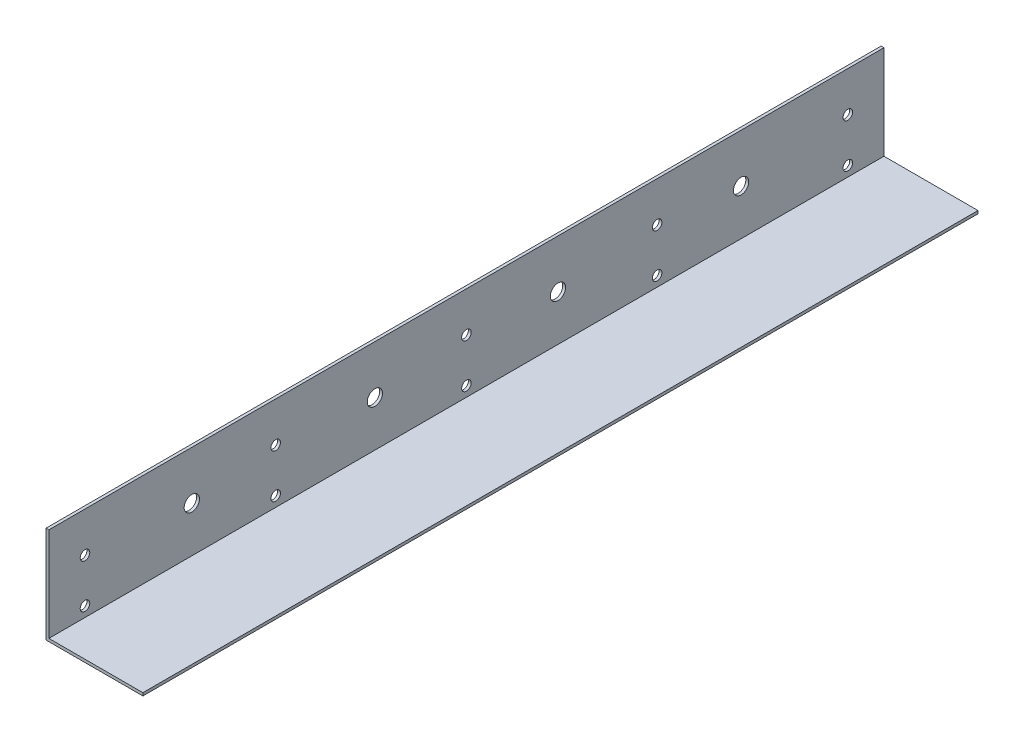
SolidWorks part; units mm, degrees
material "AISI 1015 Acero estirado en frío (SS)"
ref_plane "Alzado" through (0, 0, 0) normal (0, 0, 1) x (1, 0, 0)
ref_plane "Planta" through (0, 0, 0) normal (0, 1, 0) x (1, 0, 0)
ref_plane "Vista lateral" through (0, 0, 0) normal (1, 0, 0) x (0, 0, -1)
sketch "Croquis1" plane through (0, 0, 0) normal (0, 0, 1) x (1, 0, 0)
  line L0 (0, 0) -> (0, 50.8)
  line L1 (0, 0) -> (50.8, 0)
  line L2 (1.5, 1.5) -> (50.8, 1.5)
  line L3 (1.5, 1.5) -> (1.5, 50.8)
  line L4 (0, 50.8) -> (1.5, 50.8)
  line L5 (50.8, 1.5) -> (50.8, 0)
  dimension "D1" = 50.8
  dimension "D2" = 1.5
extrude "Saliente-Extruir1" add sketch "Croquis1" along normal blind 437.896
sketch "Croquis2" plane through (0, 0, 0) normal (-1, 0, 0) x (0, 0, 1)
  line L0 (0, 25.4) -> (437.896, 25.4) construction
  line L1 (0, 50.8) -> (0, 0) construction
  line L2 (437.896, 50.8) -> (437.896, 0) construction
  line L3 (218.948, 50.8) -> (218.948, 0) construction
  line L4 (437.896, 50.8) -> (0, 50.8) construction
  line L5 (437.896, 0) -> (0, 0) construction
  circle A0 centre (266.948, 25.4) radius 4
  circle A1 centre (362.948, 25.4) radius 4
  circle A2 centre (74.948, 25.4) radius 4
  circle A3 centre (170.948, 25.4) radius 4
  point P12 (218.948, 25.4)
  dimension "D3" = 8
  dimension "D1" = 48
  dimension "D2" = 96
extrude "Cortar-Extruir1" cut sketch "Croquis2" against normal blind 4.064
sketch "Croquis3" plane through (0, 0, 0) normal (-1, 0, 0) x (0, 0, 1)
  circle A0 centre (18.948, 29.8) radius 2.5 construction
  circle A1 centre (118.948, 29.8) radius 2.5 construction
  circle A2 centre (218.948, 29.8) radius 2.5 construction
  circle A3 centre (318.948, 29.8) radius 2.5 construction
  circle A4 centre (418.948, 29.8) radius 2.5 construction
  circle A5 centre (18.948, 29.8) radius 2.5
  circle A6 centre (118.948, 29.8) radius 2.5
  circle A7 centre (218.948, 29.8) radius 2.5
  circle A8 centre (318.948, 29.8) radius 2.5
  circle A9 centre (418.948, 29.8) radius 2.5
  circle A10 centre (18.948, 6.8) radius 2.5 construction
  circle A11 centre (218.948, 6.8) radius 2.5 construction
  circle A12 centre (118.948, 6.8) radius 2.5 construction
  circle A13 centre (318.948, 6.8) radius 2.5 construction
  circle A14 centre (418.948, 6.8) radius 2.5 construction
  circle A15 centre (18.948, 6.8) radius 2.5
  circle A16 centre (218.948, 6.8) radius 2.5
  circle A17 centre (118.948, 6.8) radius 2.5
  circle A18 centre (318.948, 6.8) radius 2.5
  circle A19 centre (418.948, 6.8) radius 2.5
extrude "Cortar-Extruir2" cut sketch "Croquis3" against normal up to surface (1.5 mm away) up to face at (1.5, 25.4, 174.948)
ref_plane "Plano1" through (0, 0, 218.948) normal (0, 0, -1) x (-1, 0, 0)
